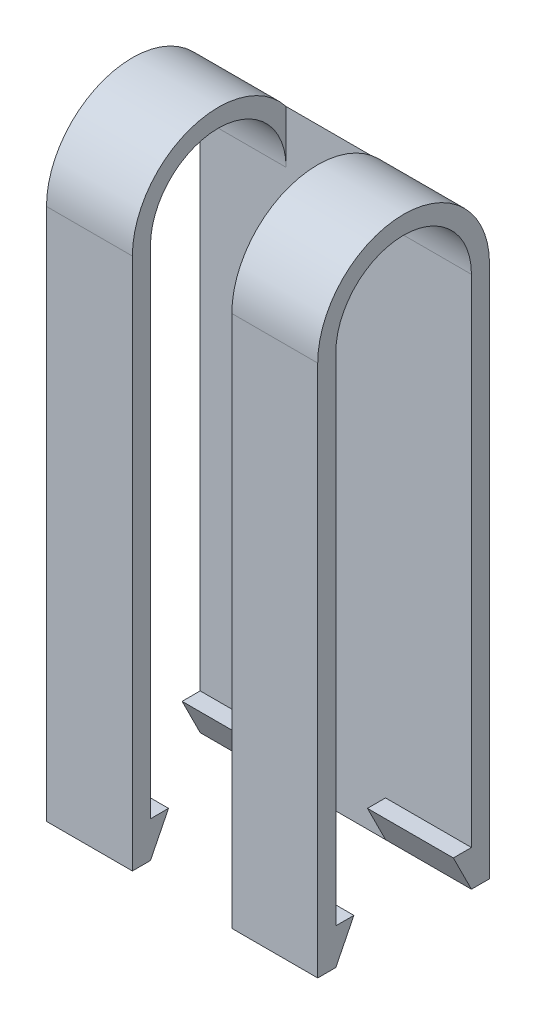
SolidWorks part; units mm, degrees
ref_plane "Front Plane" through (0, 0, 0) normal (0, 0, 1) x (1, 0, 0)
ref_plane "Top Plane" through (0, 0, 0) normal (0, 1, 0) x (1, 0, 0)
ref_plane "Right Plane" through (0, 0, 0) normal (1, 0, 0) x (0, 0, -1)
sketch "Sketch1" plane through (0, 0, 0) normal (1, 0, 0) x (0, 0, -1)
  line L0 (0, 0) -> (0, 58.9)
  line L1 (0, 58.9) -> (15, 58.9)
  line L2 (15, 58.9) -> (15, 0)
  line L3 (0, 0) -> (-2, 0)
  line L4 (-2, 0) -> (-2, 58.9)
  line L5 (15, 0) -> (17, 0)
  line L6 (17, 0) -> (17, 58.9)
  line L7 (15, 0) -> (13, 4)
  line L8 (13, 4) -> (15, 4)
  line L9 (7.5, 68.4) -> (7.5, -6.29) construction
  line L10 (0, 0) -> (2, 4)
  line L11 (2, 4) -> (0, 4)
  arc A0 (0, 58.9) -> (15, 58.9) centre (7.5, 58.9) cw
  arc A1 (-2, 58.9) -> (17, 58.9) centre (7.5, 58.9) cw
  point P11 (7.5, 68.4)
  dimension "D3" = 2
  dimension "D5" = 2
  dimension "D4" = 4
  dimension "D1" = 68.4
  dimension "D2" = 15
extrude "Boss-Extrude1" add sketch "Sketch1" against normal blind 30 contours A1 L4 L3 L0 A0 L2 L5 L6 | L9 A1 L4 L3 L0 A0 | L10 L11 L0 | L8 L7 L2 region at (0, 35.8968, 0.4338) region at (0, 2.6667, -0.6667) region at (0, 35.8968, -15.4338) region at (0, 2.6667, -14.3333)
sketch "Sketch2" plane through (0, 0, 2) normal (0, 0, 1) x (1, 0, 0)
  line L0 (-15, 68.4) -> (-15, 0) construction
  line L2 (-30, 0) -> (0, 0) construction
  line L3 (0, 68.4) -> (-30, 68.4) construction
  line L4 (-20.5, 68.4) -> (-20.5, 0)
  line L5 (-20.5, 68.4) -> (-9.5, 68.4)
  line L6 (-15, 68.4) -> (-15, 0)
  line L7 (-9.5, 0) -> (-20.5, 0)
  line L8 (-9.5, 68.4) -> (-9.5, 0)
  line M8 (0, 58.9) -> (-30, 58.9)
  line M10 (-30, 0) -> (0, 0)
  dimension "D1" = 5.5
extrude "Cut-Extrude1" cut sketch "Sketch2" against normal blind 17 contours L8 L6 M8 M10 | L6 L4 M8 M10 | L6 L5 L4 M8 | L8 L5 L6 M8 region at (-17.75, 63.65, 2) region at (-17.75, 29.45, 2) region at (-12.25, 63.65, 2) region at (-12.25, 29.45, 2)
